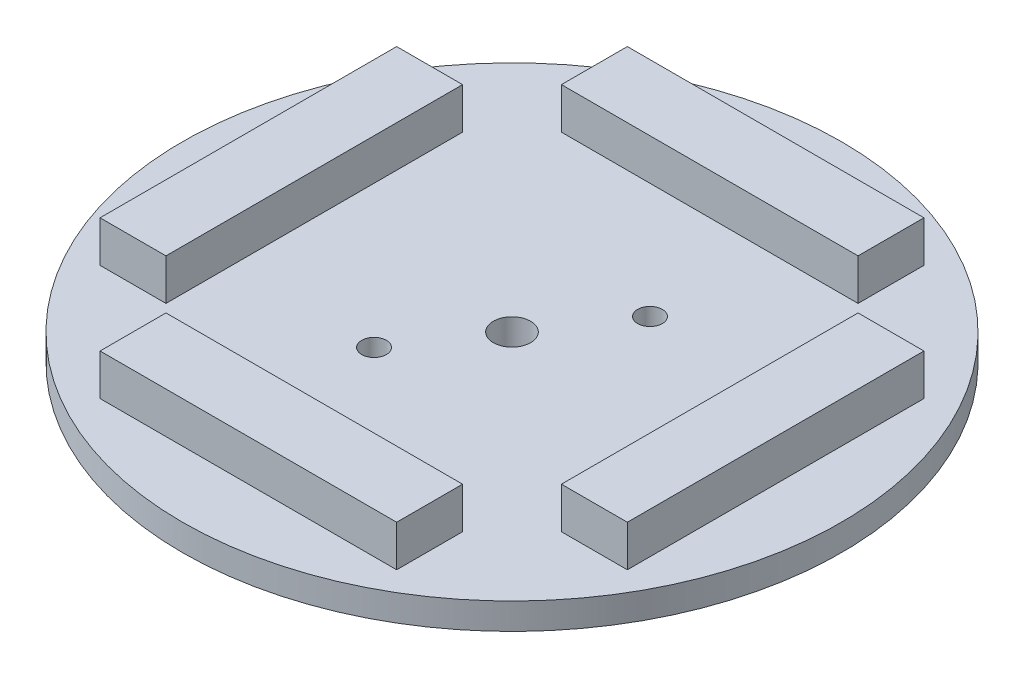
SolidWorks part; units mm, degrees
material "A-Glass Fiber"
ref_plane "Front Plane" through (0, 0, 0) normal (0, 0, 1) x (1, 0, 0)
ref_plane "Top Plane" through (0, 0, 0) normal (0, 1, 0) x (1, 0, 0)
ref_plane "Right Plane" through (0, 0, 0) normal (1, 0, 0) x (0, 0, -1)
sketch "Sketch1" plane through (0, 0, 0) normal (0, 1, 0) x (1, 0, 0)
  line L0 (-11.1839, -16.5808) -> (11.1839, 16.5808) construction
  line L1 (0, 20) -> (0, -20) construction
  circle A0 centre (0, 0) radius 20
  circle A1 centre (0, 0) radius 1.1303
  circle A2 centre (3.3725, 5) radius 0.75
  circle A3 centre (-3.3725, -5) radius 0.75
  dimension "D1" = 40
  dimension "D5" = 2.2606
  dimension "D6" = 1.5
  dimension "D7" = 1.5
  dimension "D2" = 34
  dimension "D3" = 5
  dimension "D4" = 5
extrude "PCB" add sketch "Sketch1" along normal blind 1.6 contours A0 | A3 | A1 | A2
sketch "Sketch2" plane through (0, 1.6, 0) normal (0, 1, 0) x (1, 0, 0)
  line L0 (0, 20) -> (0, 0) construction
  line L1 (-9, 16) -> (9, 16)
  line L2 (-9, 16) -> (-9, 12)
  line L3 (-9, 12) -> (9, 12)
  line L4 (9, 16) -> (9, 12)
  circle A0 centre (0, 0) radius 20 construction
  point P9 (0, 16)
  dimension "D1" = 4
  dimension "D2" = 18
  dimension "D3" = 16
extrude "Hirose Connector Stack" add sketch "Sketch2" along normal blind 2.5 contours L1 L4 L3 L2
pattern_circular "CirPattern1" count 4 over 360 about axis through (0, 1.6, 0) along (0, 1, 0) of "Hirose Connector Stack"
